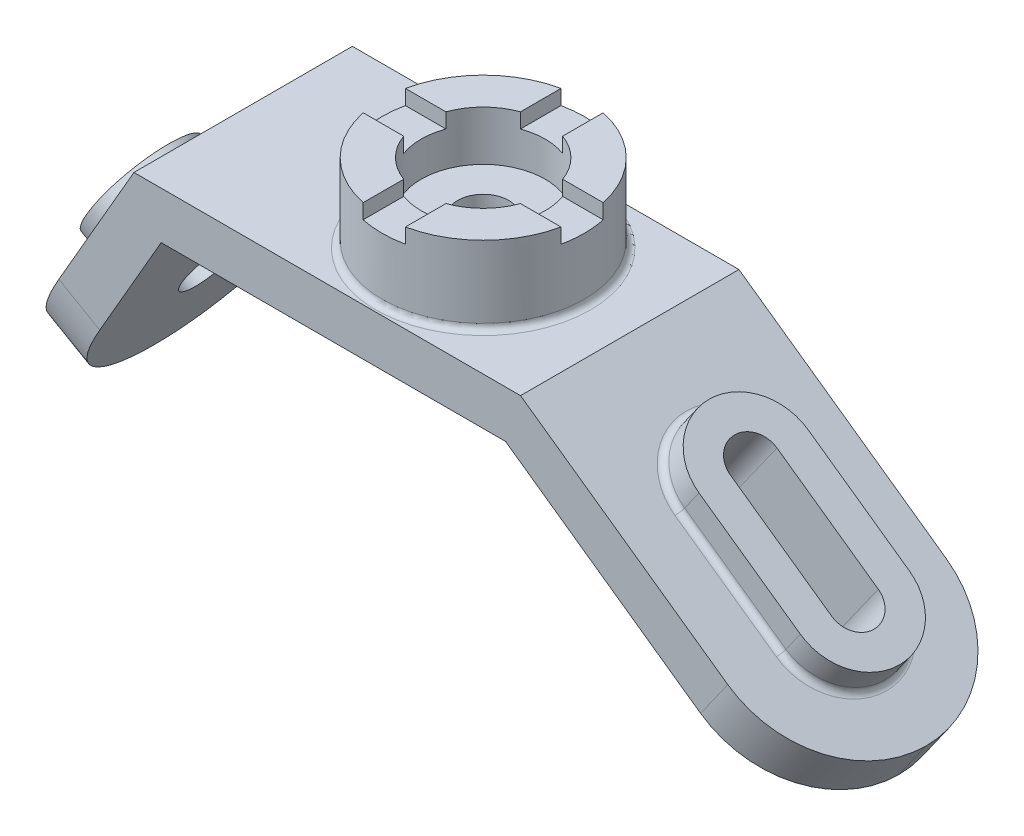
SolidWorks part; units mm, degrees
material "AISI 4340 Steel, annealed"
ref_plane "Front" through (0, 0, 0) normal (0, 0, 1) x (1, 0, 0)
ref_plane "Top" through (0, 0, 0) normal (0, 1, 0) x (1, 0, 0)
ref_plane "Right" through (0, 0, 0) normal (1, 0, 0) x (0, 0, -1)
sketch "Sketch1" plane through (0, 0, 0) normal (0, 0, 1) x (1, 0, 0)
  line L0 (-23.7568, -41.148) -> (0, 0)
  line L1 (0, 0) -> (70.4772, 0)
  line L2 (70.4772, 0) -> (128.6432, -41.148)
  line L3 (128.6432, -41.148) -> (134.2174, -33.2684)
  line L4 (134.2174, -33.2684) -> (73.5461, 9.652)
  line L5 (73.5461, 9.652) -> (-5.5726, 9.652)
  line L6 (-5.5726, 9.652) -> (-32.1157, -36.322)
  line L7 (-32.1157, -36.322) -> (-23.7568, -41.148)
  point P8 (0, 0)
  dimension "D1" = 9.652
  dimension "D2" = 9.652
  dimension "D3" = 9.652
  dimension "D4" = 152.4
  dimension "D5" = 58.166
  dimension "D6" = 120
  dimension "D7" = 41.148
extrude "Boss-Extrude1" add sketch "Sketch1" along normal mid plane 44.704
fillet "Fillet1" radius 22.352 4 edges at (-27.9362, -38.735, 22.352) (-27.9362, -38.735, -22.352) (131.4303, -37.2082, -22.352) (131.4303, -37.2082, 22.352)
sketch "Sketch2" plane through (29.0807, 41.1079, 0) normal (0.5775, 0.8164, 0) x (0.8164, -0.5775, 0)
  line L0 (106.4329, 0) -> (81.0329, 0) construction
  line L1 (106.4329, -4.7752) -> (81.0329, -4.7752)
  line L2 (106.4329, 4.7752) -> (81.0329, 4.7752)
  arc A0 (106.4329, -4.7752) -> (106.4329, 4.7752) centre (106.4329, 0) ccw
  arc A1 (81.0329, 4.7752) -> (81.0329, -4.7752) centre (81.0329, 0) ccw
  point P4 (93.7329, 0)
  dimension "D1" = 4.7752
  dimension "D2" = 25.4
extrude "Cut-Extrude1" cut sketch "Sketch2" against normal through all
sketch "Sketch3" plane through (29.0807, 41.1079, 0) normal (0.5775, 0.8164, 0) x (0.8164, -0.5775, 0)
  line L0 (81.0329, 0) -> (106.4329, 0) construction
  line L1 (81.0329, 4.7752) -> (106.4329, 4.7752)
  line L2 (81.0329, -4.7752) -> (106.4329, -4.7752)
  line L3 (81.0329, 0) -> (106.4329, 0) construction
  line L4 (81.0329, 11.176) -> (106.4329, 11.176)
  line L5 (81.0329, -11.176) -> (106.4329, -11.176)
  arc A0 (81.0329, 4.7752) -> (81.0329, -4.7752) centre (81.0329, 0) ccw
  arc A1 (106.4329, -4.7752) -> (106.4329, 4.7752) centre (106.4329, 0) ccw
  arc A2 (81.0329, 11.176) -> (81.0329, -11.176) centre (81.0329, 0) ccw
  arc A3 (106.4329, -11.176) -> (106.4329, 11.176) centre (106.4329, 0) ccw
  arc A4 (106.4329, -4.7752) -> (106.4329, 4.7752) centre (106.4329, 0) ccw construction
  point P4 (93.7329, 0)
  point P9 (93.7329, 0)
  point P16 (106.4329, 8.5056)
  dimension "D1" = 11.176
extrude "Boss-Extrude2" add sketch "Sketch3" along normal blind 6.35
sketch "Sketch4" plane through (-8.3589, 4.826, 0) normal (-0.866, 0.5, 0) x (0, 0, 1)
  circle A0 centre (0, -25.1616) radius 11.176
  dimension "D1" = 22.352
extrude "Boss-Extrude3" add sketch "Sketch4" along normal blind 6.35
hole_wizard "3/8 (0.44) Diameter Hole1" positions "Sketch5" profile "Sketch6" hole size "3/8" standard "ANSI Inch" end condition through all
sketch "Sketch5" plane through (-13.8581, 8.001, 0) normal (-0.866, 0.5, 0) x (0, 0, 1)
  point P0 (0, -25.1616)
sketch "Sketch6" plane through (-26.4389, -13.7896, 0) normal (0, 0, 1) x (-0.5, -0.866, 0)
  line L0 (0, 0) -> (0, 152.8117)
  line L1 (0, 152.8117) -> (5.588, 152.8117)
  line L2 (5.588, 152.8117) -> (5.588, 0)
  line L5 (5.588, 0) -> (0, 0)
  line L11 (0, -6.35) -> (0, 107.95) construction
  dimension "Thru Hole Dia." = 11.176
  dimension "Thru Hole Depth" = 152.8117
sketch "Sketch7" plane through (0, 9.652, 0) normal (0, 1, 0) x (1, 0, 0)
  line L0 (-5.5726, -22.352) -> (-5.5726, 22.352) construction
  circle A0 centre (43.551, 0) radius 20.701
  point P4 (0, 0)
  dimension "D2" = 41.402
  dimension "D1" = 49.1236
extrude "Boss-Extrude4" add sketch "Sketch7" along normal blind 16.002
sketch "Sketch8" plane through (0, 25.654, 0) normal (0, 1, 0) x (1, 0, 0)
  line L0 (23.3054, 4.318) -> (63.7967, 4.318)
  line L1 (63.7967, 4.318) -> (63.7967, -4.318) construction
  line L2 (63.7967, -4.318) -> (23.3054, -4.318)
  line L3 (23.3054, -4.318) -> (39.233, 20.2456) construction
  line L4 (39.233, 20.2456) -> (39.233, -20.2456)
  line L5 (39.233, -20.2456) -> (47.869, -20.2456) construction
  line L6 (47.869, -20.2456) -> (47.869, 20.2456)
  line L7 (47.869, 20.2456) -> (39.233, 20.2456) construction
  circle A0 centre (43.551, 0) radius 20.701 construction
  circle A1 centre (43.551, 0) radius 20.701 construction
  arc A2 (23.3054, 4.318) -> (23.3054, -4.318) centre (43.551, 0) ccw
  arc A3 (47.869, 20.2456) -> (39.233, 20.2456) centre (43.551, 0) ccw
  arc A4 (63.7967, -4.318) -> (63.7967, 4.318) centre (43.551, 0) ccw
  arc A5 (39.233, -20.2456) -> (47.869, -20.2456) centre (43.551, 0) ccw
  circle M10 centre (43.551, 0) radius 20.701
  dimension "D1" = 8.636
extrude "Cut-Extrude2" cut sketch "Sketch8" against normal blind 3.048 contours L0 L6 L4 M10 | L2 L6 L0 L4 | L6 L2 L0 M10 | L6 L2 L4 M10 | L4 L0 L2 M10 region at (31.1165, 25.654, 0) region at (43.551, 25.654, -12.4345) region at (43.551, 25.654, 0) region at (55.9855, 25.654, 0) region at (43.551, 25.654, 12.4345)
hole_wizard "CBORE for 3/8 Binding Head Machine Screw1" positions "Sketch9" profile "Sketch10" counterbore size "3/8" standard "ANSI Inch" end condition through all
sketch "Sketch9" plane through (0, 25.654, 0) normal (0, 1, 0) x (1, 0, 0)
  point P0 (43.551, 0)
sketch "Sketch10" plane through (43.551, 25.654, 0) normal (1, 0, 0) x (0, 0, 1)
  line L0 (0, 0) -> (0, 66.802)
  line L1 (0, 66.802) -> (5.207, 66.802)
  line L3 (5.207, 66.802) -> (5.207, 10.16)
  line L4 (5.207, 10.16) -> (12.7, 10.16)
  line L5 (12.7, 10.16) -> (12.7, 0)
  line L7 (12.7, 0) -> (0, 0)
  line L11 (0, -6.35) -> (0, 107.95) construction
  dimension "Thru Hole Dia." = 10.414
  dimension "Thru Hole Depth" = 66.802
  dimension "C'Bore Dia." = 25.4
  dimension "C'Bore Depth" = 10.16
fillet "Fillet2" radius 1.27 6 edges at (105.6019, -13.025, -11.176) (125.0936, -26.814, 0) (105.6019, -13.025, 11.176) (-15.3517, -7.2859, 0) (86.1101, 0.7639, 0) (22.85, 9.652, 0)
